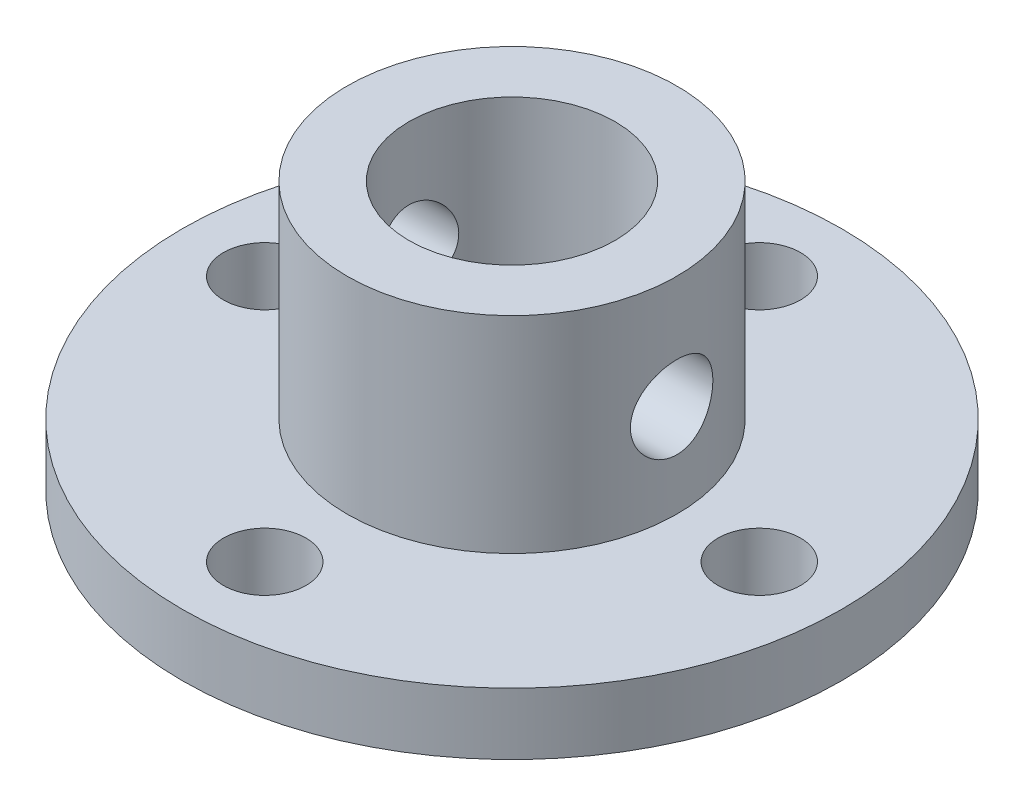
SolidWorks part; units mm, degrees
ref_plane "前视基准面" through (0, 0, 0) normal (0, 0, 1) x (1, 0, 0)
ref_plane "上视基准面" through (0, 0, 0) normal (0, 1, 0) x (1, 0, 0)
ref_plane "右视基准面" through (0, 0, 0) normal (1, 0, 0) x (0, 0, -1)
other "Configuration Table"
sketch "草图1" plane through (0, 0, 0) normal (0, 1, 0) x (1, 0, 0)
  line L0 (0, 0) -> (0, 12) construction
  line L1 (0, 0) -> (12, 0) construction
  circle A0 centre (0, 0) radius 16
  circle A1 centre (0, 0) radius 12 construction
  circle A2 centre (0, 12) radius 2
  circle A3 centre (12, 0) radius 2
  circle A4 centre (0, -12) radius 2
  circle A5 centre (-12, 0) radius 2
  circle A6 centre (0, 0) radius 5
  dimension "D1" = 32
  dimension "D2" = 24
  dimension "D3" = 4
  dimension "D4" = 4
  dimension "D5" = 10
extrude "凸台-拉伸1" add sketch "草图1" along normal blind 3
sketch "草图2" plane through (0, 3, 0) normal (0, 1, 0) x (1, 0, 0)
  circle A0 centre (0, 0) radius 8
  circle A1 centre (0, 0) radius 5
  dimension "D1" = 16
  dimension "D2" = 10
extrude "凸台-拉伸2" add sketch "草图2" along normal blind 10
sketch "草图3" plane through (0, 0, 0) normal (1, 0, 0) x (0, 0, -1)
  line L0 (-16, 0) -> (16, 0) construction
  circle A0 centre (0, 7.5) radius 2
  dimension "D1" = 4
  dimension "D2" = 7.5
extrude "切除-拉伸1" cut sketch "草图3" against normal blind 10 and the other way blind 10
